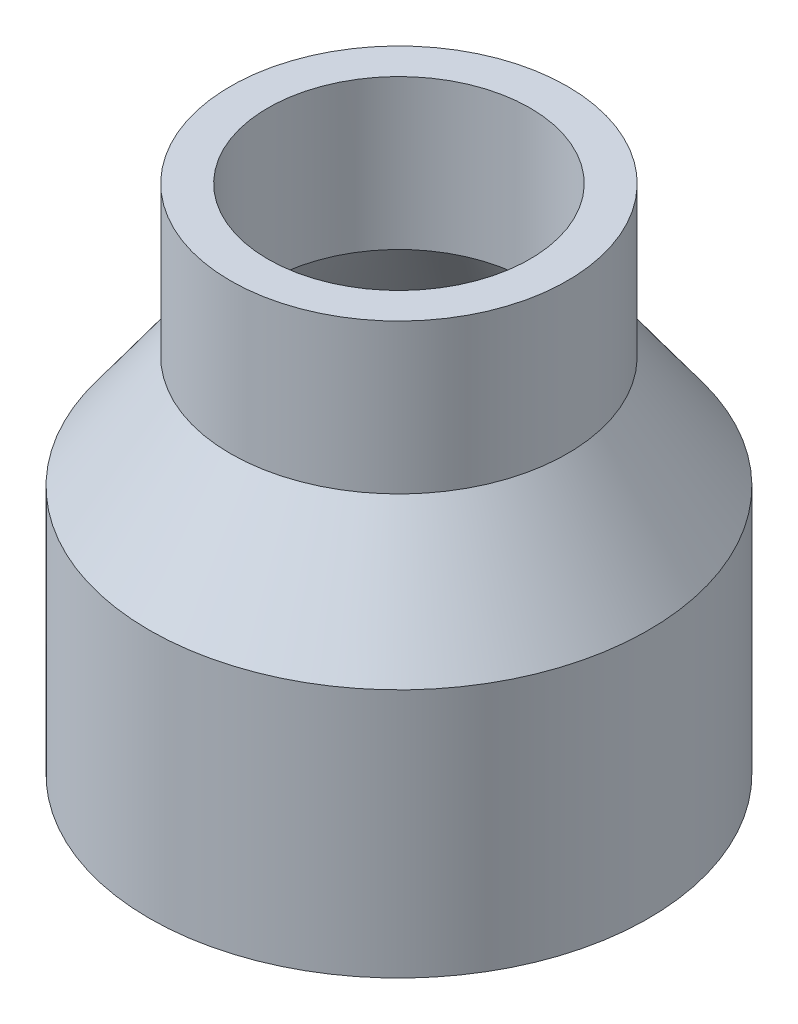
SolidWorks part; units mm, degrees
ref_plane "Front Plane" through (0, 0, 0) normal (0, 0, 1) x (1, 0, 0)
ref_plane "Top Plane" through (0, 0, 0) normal (0, 1, 0) x (1, 0, 0)
ref_plane "Right Plane" through (0, 0, 0) normal (1, 0, 0) x (0, 0, -1)
sketch "Sketch1" plane through (0, 0, 0) normal (0, 1, 0) x (1, 0, 0)
  circle A0 centre (0, 0) radius 8
  circle A1 centre (0, 0) radius 10
  dimension "D1" = 16
  dimension "D2" = 20
extrude "Boss-Extrude1" add sketch "Sketch1" along normal blind 10
ref_plane "Plane1" through (0, 14.5, 0) normal (0, 1, 0) x (1, 0, 0)
sketch "Sketch2" plane through (0, 14.5, 0) normal (0, 1, 0) x (1, 0, 0)
  circle A0 centre (0, 0) radius 5.25
  circle A1 centre (0, 0) radius 6.75
  dimension "D1" = 10.5
  dimension "D2" = 13.5
extrude "Boss-Extrude2" add sketch "Sketch2" along normal blind 6 separate body
sketch "Sketch5" plane through (0, 0, 0) normal (0, 0, 1) x (1, 0, 0)
  line L0 (-6.75, 14.5) -> (-10, 10)
  line L1 (-6.75, 20.5) -> (-6.75, 14.5) construction
  line L2 (10, 10) -> (-10, 10) construction
  line L3 (-10, 10) -> (-8, 10)
  line L4 (-8, 10) -> (-5.25, 14.5)
  line L5 (-5.25, 14.5) -> (-6.75, 14.5)
  line L6 (0, 10.1521) -> (0, 14.5)
  dimension "D1" = 2
  dimension "D2" = 1.5
revolve "Revolve2" add sketch "Sketch5" angle 360 about L6 region at (-7.5714, 12.1429, 0)
thread "Thread1" pitch 1 method extrude profile "Thread Profile1" start angle 0, offset 0, length 0, pitch 1, diameter 16
ref_plane "Plane4" through (8, 0, 0) normal (0, 0, 1) x (1, 0, 0)
sketch "Thread Profile1" plane through (8, 0, 0) normal (0, 0, 1) x (1, 0, 0)
  line L0 (0, 0) -> (0, 1) construction
  line L11 (0, 0) -> (0, 0.875)
  line L12 (0, 0.875) -> (-0.5413, 0.5625)
  line L13 (-0.5413, 0.5625) -> (-0.5413, 0.3125)
  line L15 (-0.5413, 0.3125) -> (0, 0)
  line L17 (-0.5413, 0.4375) -> (0, 0.4375) construction
  point P2 (0, 0)
  dimension "Pitch" = 1
  dimension "Profile_Angle" = 60
  dimension "Profile_Land" = 0.25
  dimension "Profile_Height" = 0.5413
